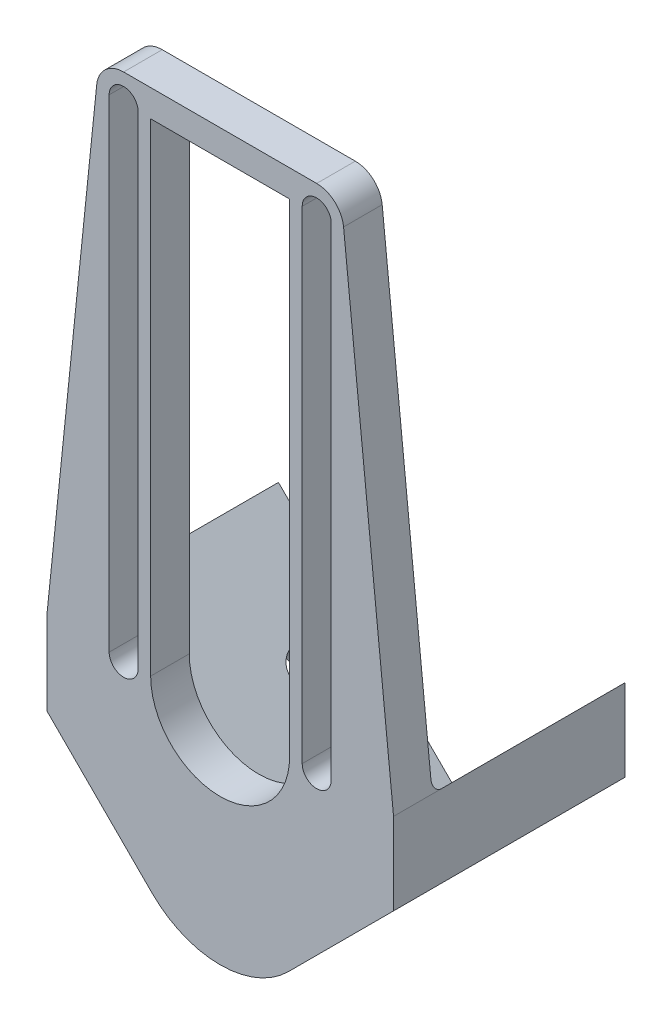
SolidWorks part; units mm, degrees
ref_plane "Alzado" through (0, 0, 0) normal (0, 0, 1) x (1, 0, 0)
ref_plane "Planta" through (0, 0, 0) normal (0, 1, 0) x (1, 0, 0)
ref_plane "Vista lateral" through (0, 0, 0) normal (1, 0, 0) x (0, 0, -1)
sketch "Croquis2" plane through (0, 0, 0) normal (0, 0, 1) x (1, 0, 0)
  line L0 (0, 0) -> (17.9605, 17.9605)
  line L1 (17.9605, 17.9605) -> (17.9605, 9.4752)
  line L2 (17.9605, 9.4752) -> (0, -8.4853)
  line L3 (0, -8.4853) -> (0, 0)
  line L4 (0, 0) -> (0, 17.9605) construction
  line L5 (0, 17.9605) -> (17.9605, 17.9605) construction
  line L6 (10, 17.9605) -> (10, 67.9605) construction
  line L7 (8.5, 67.9605) -> (8.5, 17.9605)
  line L8 (11.5, 67.9605) -> (11.5, 17.9605)
  line L9 (7.2, 67.9605) -> (7.2, 17.9605)
  line L10 (12.8, 67.9605) -> (12.8, 17.9605)
  line L11 (17.9605, 17.9605) -> (12.7853, 68.2472)
  line L12 (0, 10.7605) -> (0, 0)
  line L13 (0, 17.9605) -> (0, 67.9605) construction
  line L14 (-7.2, 67.9605) -> (7.2, 67.9605)
  line L15 (0, 67.9605) -> (0, 70.7605)
  line L16 (-10, 70.7605) -> (10, 70.7605)
  line L17 (-17.9605, 9.4752) -> (0, -8.4853)
  line L18 (0, 0) -> (-17.9605, 17.9605)
  line L19 (-17.9605, 17.9605) -> (-17.9605, 9.4752)
  line L20 (-17.9605, 17.9605) -> (-12.7853, 68.2472)
  line L21 (-12.8, 67.9605) -> (-12.8, 17.9605)
  line L22 (-11.5, 67.9605) -> (-11.5, 17.9605)
  line L23 (-8.5, 67.9605) -> (-8.5, 17.9605)
  line L24 (-7.2, 67.9605) -> (-7.2, 17.9605)
  arc A0 (8.5, 17.9605) -> (11.5, 17.9605) centre (10, 17.9605) ccw
  arc A1 (11.5, 67.9605) -> (8.5, 67.9605) centre (10, 67.9605) ccw
  arc A2 (7.2, 17.9605) -> (12.8, 17.9605) centre (10, 17.9605) ccw
  arc A3 (12.8, 67.9605) -> (7.2, 67.9605) centre (10, 67.9605) ccw
  arc A4 (7.2, 17.9605) -> (-7.2, 17.9605) centre (0, 17.9605) cw
  arc A5 (-7.2, 17.9605) -> (-12.8, 17.9605) centre (-10, 17.9605) cw
  arc A6 (-8.5, 17.9605) -> (-11.5, 17.9605) centre (-10, 17.9605) cw
  arc A7 (-11.5, 67.9605) -> (-8.5, 67.9605) centre (-10, 67.9605) cw
  arc A8 (-12.8, 67.9605) -> (-7.2, 67.9605) centre (-10, 67.9605) cw
  dimension "D4" = 3
  dimension "D6" = 5.6
  dimension "D2" = 6
  dimension "D3" = 10
  dimension "D5" = 50
extrude "Saliente-Extruir1" add sketch "Croquis2" against normal blind 20 contours L18 L19 L17 L3 | L3 L2 L1 L0 region at (8.9803, 4.7376, 0) region at (-8.9803, 4.7376, 0)
extrude "Saliente-Extruir2" add sketch "Croquis2<3>" along normal blind 4 contours L18 L19 L17 L3 | L21 A8 L20 L18 L12 A4 A5 | A2 A4 L12 L0 L11 A3 L10 | L3 L2 L1 L0 | L10 A3 L9 A2 A1 L8 A0 L7 | A8 L21 A5 L24 L22 A7 L23 A6 | L16 A8 L14 L15 | A3 L16 L15 L14 region at (0.7057, 5.3803, 0) region at (8.9803, 4.7376, 0) region at (-8.4812, 9.4793, 0) region at (-8.9803, 4.7376, 0) region at (12.2382, 68.0754, 0) region at (-10, 15.7193, 0) region at (3.9255, 69.4202, 0) region at (-3.9255, 69.4202, 0)
sketch "Croquis2<3>" plane through (0, 0, 0) normal (0, 0, 1) x (1, 0, 0) same geometry as "Croquis2"
fillet "Redondeo1" radius 1 2 edges at (-8.9803, 8.9803, 0) (8.9803, 8.9803, 0)
fillet "Redondeo2" radius 10 1 edges at (0, -8.4853, -8)
ref_plane "Plano1" through (0, 0, 0) normal (0.7071, 0.7071, 0) x (0, 0, -1)
sketch "Croquis3" plane through (0, 0, 0) normal (0.7071, 0.7071, 0) x (0, 0, -1)
  line L0 (20, 12.7) -> (14, 12.7) construction
  line L1 (20, 0) -> (20, 25.4) construction
  circle A0 centre (14, 12.7) radius 1.8
  dimension "D1" = 3.6
  dimension "D2" = 6
extrude "Cortar-Extruir1" cut sketch "Croquis3" against normal up to surface (6 mm away) up to face at (-12.5158, 4.0305, -8)
ref_plane "Plano2" through (0, 0, 0) normal (-0.7071, 0.7071, 0) x (0, 0, 1)
sketch "Croquis4" plane through (0, 0, 0) normal (-0.7071, 0.7071, 0) x (0, 0, 1)
  line L0 (-20, 12.7) -> (-14, 12.7) construction
  line L1 (-20, 0) -> (-20, 25.4) construction
  circle A0 centre (-14, 12.7) radius 1.8
  dimension "D2" = 3.6
  dimension "D1" = 6
extrude "Cortar-Extruir2" cut sketch "Croquis4" against normal up to surface (6 mm away) up to face at (12.5158, 4.0305, -8)
ref_plane "Plano3" through (4.2426, -4.2426, 0) normal (0.7071, -0.7071, 0) x (0, 0, -1)
sketch "Croquis5" plane through (4.2426, -4.2426, 0) normal (0.7071, -0.7071, 0) x (0, 0, -1)
  circle A0 centre (14, 12.7) radius 3.2
  dimension "D1" = 6.4
extrude "Cortar-Extruir3" cut sketch "Croquis5" against normal blind 4
ref_plane "Plano4" through (-4.2426, -4.2426, 0) normal (-0.7071, -0.7071, 0) x (0, 0, 1)
sketch "Croquis6" plane through (-4.2426, -4.2426, 0) normal (-0.7071, -0.7071, 0) x (0, 0, 1)
  circle A0 centre (-14, 12.7) radius 3.2
  dimension "D1" = 6.4
extrude "Cortar-Extruir4" cut sketch "Croquis6" against normal blind 4
